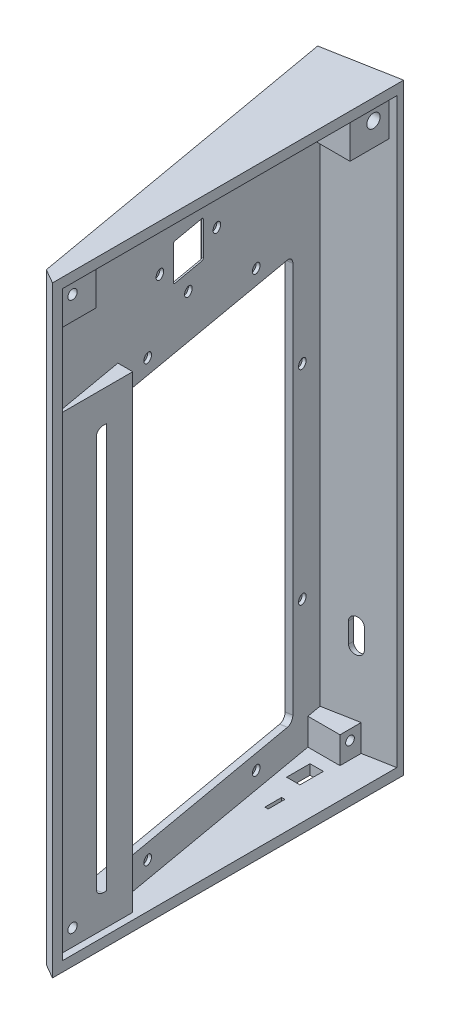
SolidWorks part; units mm, degrees
ref_plane "前视基准面" through (0, 0, 0) normal (0, 0, 1) x (1, 0, 0)
ref_plane "上视基准面" through (0, 0, 0) normal (0, 1, 0) x (1, 0, 0)
ref_plane "右视基准面" through (0, 0, 0) normal (1, 0, 0) x (0, 0, -1)
other "Configuration Table"
sketch "草图1" plane through (0, 0, 0) normal (0, 1, 0) x (1, 0, 0)
  line L0 (82.9035, -37.3993) -> (82.9035, -142.3993)
  line L1 (82.9035, -142.3993) -> (78.5734, -139.8993)
  line L2 (78.5734, -139.8993) -> (61.2086, -41.4185)
  line L3 (61.2086, -41.4185) -> (82.9035, -37.3993)
  dimension "D1" = 100
  dimension "D2" = 105
  dimension "D3" = 5
  dimension "D4" = 170
  dimension "D5" = 60
  dimension "D6" = 90.496
  dimension "D7" = 79.504
extrude "凸台-拉伸1" add sketch "草图1" along normal blind 180
sketch "草图5" plane through (52.2799, 0, -9.2184) normal (-0.9848, 0, 0.1736) x (0.1736, 0, 0.9848)
  line L0 (51.418, 180) -> (51.418, 0) construction
  line L1 (139.418, 12.5) -> (63.418, 12.5)
  line L2 (139.418, 12.5) -> (139.418, 133.5)
  line L3 (139.418, 133.5) -> (63.418, 133.5)
  line L4 (63.418, 12.5) -> (63.418, 133.5)
  line L5 (151.418, 180) -> (151.418, 0) construction
  line L6 (51.418, 0) -> (151.418, 0) construction
  dimension "D1" = 76
  dimension "D2" = 121
  dimension "D3" = 12
  dimension "D4" = 12
  dimension "D5" = 12.5
extrude "切除-拉伸2" cut sketch "草图5" against normal blind 2
sketch "草图7" plane through (82.9035, 0, 0) normal (1, 0, 0) x (0, 0, -1)
  line L8 (-139.3993, 3) -> (-40.3993, 3)
  line L9 (-40.3993, 3) -> (-40.3993, 177)
  line L10 (-40.3993, 177) -> (-139.3993, 177)
  line L11 (-139.3993, 177) -> (-139.3993, 3)
  line L12 (-139.3993, 3) -> (-40.3993, 3)
  line L13 (-40.3993, 3) -> (-40.3993, 177)
  line L14 (-40.3993, 177) -> (-139.3993, 177)
  line L15 (-139.3993, 177) -> (-139.3993, 3)
  dimension "D1" = 3
extrude "切除-拉伸3" cut sketch "草图7" against normal up to surface (19.8438 mm away) up to face at (71.8606, 73, 90.3116)
sketch "草图10" plane through (54.2496, 0, -9.5657) normal (0.9848, 0, -0.1736) x (-0.1736, 0, -0.9848)
  line L1 (-63.418, 12.5) -> (-59.918, 12.5) construction
  line L2 (-63.418, 12.5) -> (-63.418, 42.5) construction
  line L3 (-63.418, 42.5) -> (-59.918, 42.5) construction
  line L4 (-59.918, 12.5) -> (-59.918, 42.5) construction
  line L5 (-63.418, 133.5) -> (-59.918, 133.5) construction
  line L6 (-63.418, 133.5) -> (-63.418, 103.5) construction
  line L7 (-63.418, 103.5) -> (-59.918, 103.5) construction
  line L8 (-59.918, 133.5) -> (-59.918, 103.5) construction
  circle A0 centre (-59.918, 103.5) radius 1.4
  circle A1 centre (-59.918, 42.5) radius 1.4
  dimension "D1" = 30
  dimension "D2" = 30
  dimension "D3" = 3.5
  dimension "D4" = 3.5
extrude "切除-拉伸5" cut sketch "草图10" against normal blind 1
sketch "草图11" plane through (54.2496, 0, -9.5657) normal (0.9848, 0, -0.1736) x (-0.1736, 0, -0.9848)
  line L0 (-76.918, 8) -> (-116.918, 8) construction
  line L1 (-63.418, 133.5) -> (-76.918, 133.5) construction
  line L2 (-63.418, 133.5) -> (-63.418, 138) construction
  line L3 (-63.418, 138) -> (-76.918, 138) construction
  line L4 (-76.918, 133.5) -> (-76.918, 138) construction
  line L5 (-63.418, 12.5) -> (-76.918, 12.5) construction
  line L6 (-63.418, 12.5) -> (-63.418, 8) construction
  line L7 (-63.418, 8) -> (-76.918, 8) construction
  line L8 (-76.918, 12.5) -> (-76.918, 8) construction
  line L9 (-76.918, 138) -> (-116.918, 138) construction
  circle A0 centre (-116.918, 138) radius 1.4
  circle A1 centre (-76.918, 138) radius 1.4
  circle A2 centre (-116.918, 8) radius 1.4
  circle A3 centre (-76.918, 8) radius 1.4
  dimension "D1" = 13.5
  dimension "D2" = 4.5
  dimension "D3" = 13.5
  dimension "D4" = 4.5
  dimension "D5" = 40
  dimension "D6" = 40
extrude "切除-拉伸6" cut sketch "草图11" against normal blind 1
sketch "草图12" plane through (82.9035, 0, 0) normal (1, 0, 0) x (0, 0, -1)
  line L1 (-139.3993, 3) -> (-116.3993, 3)
  line L2 (-139.3993, 3) -> (-139.3993, 143)
  line L3 (-139.3993, 143) -> (-116.3993, 143)
  line L4 (-116.3993, 3) -> (-116.3993, 143)
  line L6 (-127.7343, 133.5) -> (-52.8889, 133.5) construction
  dimension "D1" = 9.5
  dimension "D2" = 23
extrude "凸台-拉伸3" add sketch "草图12" against normal up to surface (2.3874 mm away) up to face at (67.3631, 138, 64.8051)
sketch "草图13" plane through (54.2496, 0, -9.5657) normal (-0.9848, 0, 0.1736) x (0.1736, 0, 0.9848)
  line L4 (127.9081, 12.5) -> (139.418, 12.5)
  line L5 (139.418, 12.5) -> (139.418, 133.5)
  line L6 (139.418, 133.5) -> (127.9081, 133.5)
  line L7 (127.9081, 133.5) -> (127.9081, 12.5)
  line L8 (127.9081, 12.5) -> (139.418, 12.5)
  line L9 (139.418, 12.5) -> (139.418, 133.5)
  line L10 (139.418, 133.5) -> (127.9081, 133.5)
  line L11 (127.9081, 133.5) -> (127.9081, 12.5)
  dimension "D1" = 0
extrude "切除-拉伸7" cut sketch "草图13" against normal blind 2
sketch "草图14" plane through (52.2799, 0, -9.2184) normal (-0.9848, 0, 0.1736) x (0.1736, 0, 0.9848)
  line L0 (51.418, 180) -> (51.418, 0) construction
  line L1 (96.418, 151.5) -> (107.418, 151.5)
  line L2 (96.418, 151.5) -> (96.418, 162.5)
  line L3 (96.418, 162.5) -> (107.418, 162.5)
  line L4 (107.418, 151.5) -> (107.418, 162.5)
  line L5 (139.418, 133.5) -> (63.418, 133.5) construction
  line L6 (51.418, 180) -> (151.418, 180) construction
  dimension "D1" = 11
  dimension "D2" = 11
  dimension "D3" = 45
  dimension "D4" = 18
  dimension "D5" = 17.5
extrude "切除-拉伸8" cut sketch "草图14" against normal blind 2
sketch "草图17" plane through (9.4497, 0, 51.0074) normal (-0.1822, 0, -0.9833) x (-0.9833, 0, 0.1822)
  line L1 (-74.7037, 180) -> (-52.6396, 180)
  line L2 (-74.7037, 180) -> (-74.7037, 0)
  line L3 (-74.7037, 0) -> (-52.6396, 0)
  line L4 (-52.6396, 180) -> (-52.6396, 0)
extrude "凸台-拉伸9" add sketch "草图17" against normal blind 2
sketch "草图18" plane through (0, 0, 0) normal (0, -1, 0) x (1, 0, 0)
  line L0 (82.9035, 39.4333) -> (82.9035, 37.3993)
  line L1 (83.2679, 39.3658) -> (82.9035, 39.4333) construction
  line L2 (83.2679, 39.3658) -> (82.9035, 37.3993) construction
  line L3 (83.2679, 39.3658) -> (82.9035, 37.3993)
  line L4 (83.2679, 39.3658) -> (82.9035, 39.4333)
extrude "切除-拉伸9" cut sketch "草图18" against normal up to surface (180 mm away) up to face at (78.6267, 180, 73.3192)
sketch "草图19" plane through (0, 3, 0) normal (0, 1, 0) x (1, 0, 0)
  line L0 (82.9035, -40.3993) -> (82.9035, -36.7908) construction
  line L1 (77.596, -40.4166) -> (82.9035, -39.4333)
  line L2 (63.5225, -43.0238) -> (77.6894, -40.3993) construction
  line L3 (82.9035, -39.4333) -> (82.9035, -40.3993)
  line L4 (82.9035, -40.3993) -> (77.596, -40.4166)
extrude "切除-拉伸10" cut sketch "草图19" along normal up to surface (174 mm away) up to face at (77.507, 177, 80.5242)
sketch "草图20" plane through (82.9035, 0, 0) normal (1, 0, 0) x (0, 0, -1)
  line L1 (-139.3993, 143) -> (-116.3993, 143)
  line L2 (-139.3993, 143) -> (-139.3993, 3)
  line L3 (-139.3993, 3) -> (-116.3993, 3)
  line L4 (-116.3993, 143) -> (-116.3993, 3)
extrude "切除-拉伸11" cut sketch "草图20" against normal blind 2
sketch "草图21" plane through (54.2496, 0, -9.5657) normal (0.9848, 0, -0.1736) x (-0.1736, 0, -0.9848)
  line L0 (-107.418, 157) -> (-112.418, 157) construction
  line L1 (-107.418, 151.5) -> (-107.418, 162.5) construction
  line L2 (-101.918, 162.5) -> (-101.918, 167.5) construction
  line L3 (-107.418, 162.5) -> (-96.418, 162.5) construction
  line L4 (-96.418, 157) -> (-91.418, 157) construction
  line L5 (-96.418, 162.5) -> (-96.418, 151.5) construction
  line L6 (-101.918, 151.5) -> (-101.918, 146.5) construction
  line L7 (-96.418, 151.5) -> (-107.418, 151.5) construction
  circle A0 centre (-112.418, 157) radius 1.4
  circle A1 centre (-91.418, 157) radius 1.4
  circle A2 centre (-101.918, 146.5) radius 1.4
  circle A3 centre (-101.918, 167.5) radius 1.4
  dimension "D1" = 5
extrude "切除-拉伸12" cut sketch "草图21" against normal blind 1
sketch "草图23" plane through (80.9035, 0, 0) normal (1, 0, 0) x (0, 0, -1)
  line L0 (-51.4333, 8) -> (-51.4333, 26.4031) construction
  line L1 (-139.3993, 3) -> (-127.3993, 3)
  line L2 (-139.3993, 3) -> (-139.3993, 15)
  line L3 (-139.3993, 15) -> (-127.3993, 15)
  line L4 (-127.3993, 3) -> (-127.3993, 15)
  line L5 (-39.4333, 177) -> (-139.3993, 177) construction
  line L11 (-51.4333, 165) -> (-39.4333, 165)
  line L12 (-51.4333, 165) -> (-51.4333, 177)
  line L13 (-51.4333, 177) -> (-39.4333, 177)
  line L14 (-39.4333, 165) -> (-39.4333, 177)
  line L15 (-127.3993, 8) -> (-127.3993, 23.4787) construction
  line L17 (-127.3993, 165) -> (-139.3993, 165)
  line L18 (-127.3993, 165) -> (-127.3993, 177)
  line L19 (-127.3993, 177) -> (-139.3993, 177)
  line L20 (-139.3993, 165) -> (-139.3993, 177)
  dimension "D1" = 12
  dimension "D2" = 12
  dimension "D5" = 0
  dimension "D6" = 12
  dimension "D7" = 12
  dimension "D8" = 12
  dimension "D9" = 12
  dimension "D11" = 0
extrude "凸台-拉伸10" add sketch "草图23" against normal up to surface (0.3874 mm away) up to face at (73.5276, 157, 99.7657)
fillet "圆角4" radius 2 5 edges at (64.2772, 133.5, 53.0625) (78.4592, 133.5, 127.7343) (64.2772, 12.5, 53.0625) (77.4744, 12.5, 127.9079) (80.394, 12.5, 127.3931)
sketch "草图26" plane through (0, 177, 0) normal (0, 1, 0) x (1, 0, 0)
  line L3 (63.1752, -41.0542) -> (71.9242, -39.4333)
  line L4 (71.9242, -39.4333) -> (62.8894, -39.4333)
  line L5 (62.8894, -39.4333) -> (63.1752, -41.0542)
  line L6 (63.1752, -41.0542) -> (71.9242, -39.4333)
  line L7 (71.9242, -39.4333) -> (62.8894, -39.4333)
  line L8 (62.8894, -39.4333) -> (63.1752, -41.0542)
  dimension "D1" = 0
extrude "切除-拉伸15" cut sketch "草图26" against normal up to next
sketch "草图27" plane through (82.9035, 0, 0) normal (1, 0, 0) x (0, 0, -1)
  line L1 (-39.4333, 3) -> (-47.4333, 3)
  line L2 (-39.4333, 3) -> (-39.4333, 11)
  line L3 (-39.4333, 11) -> (-47.4333, 11)
  line L4 (-47.4333, 3) -> (-47.4333, 11)
  dimension "D1" = 8
  dimension "D2" = 8
extrude "凸台-拉伸11" add sketch "草图27" against normal up to surface (18.6035 mm away) up to face at (73.5276, 157, 99.7657)
sketch "草图28" plane through (82.9035, 0, 0) normal (1, 0, 0) x (0, 0, -1)
  line L1 (-47.4333, 3) -> (-39.4333, 3)
  line L2 (-47.4333, 3) -> (-47.4333, 11)
  line L3 (-47.4333, 11) -> (-39.4333, 11)
  line L4 (-39.4333, 3) -> (-39.4333, 11)
extrude "切除-拉伸16" cut sketch "草图28" against normal blind 9
sketch "草图29" plane through (0, 11, 0) normal (0, -1, 0) x (1, 0, 0)
  line L3 (73.9035, 41.1006) -> (73.9035, 39.4333)
  line L4 (73.9035, 39.4333) -> (82.9035, 39.4333)
  line L5 (82.9035, 39.4333) -> (73.9035, 41.1006)
  line L6 (73.9035, 41.1006) -> (73.9035, 39.4333)
  line L7 (73.9035, 39.4333) -> (82.9035, 39.4333)
  line L11 (82.9035, 39.4333) -> (73.9035, 41.1006)
  dimension "D1" = 0
extrude "凸台-拉伸12" add sketch "草图29" along normal up to surface (8 mm away) up to face at (77.0227, 3, 85.6663)
sketch "草图30" plane through (0, 3, 0) normal (0, -1, 0) x (1, 0, 0)
  line L3 (71.9242, 39.4333) -> (63.1752, 41.0542)
  line L4 (63.1752, 41.0542) -> (62.8894, 39.4333)
  line L5 (62.8894, 39.4333) -> (71.9242, 39.4333)
  line L6 (71.9242, 39.4333) -> (63.1752, 41.0542)
  line L7 (63.1752, 41.0542) -> (62.8894, 39.4333)
  line L8 (62.8894, 39.4333) -> (71.9242, 39.4333)
  dimension "D1" = 0
extrude "切除-拉伸17" cut sketch "草图30" against normal up to next
sketch "草图31" plane through (0, 0, 0) normal (0, -1, 0) x (1, 0, 0)
  line L1 (82.9035, 37.3993) -> (68.9035, 37.3993) construction
  line L2 (82.9035, 37.3993) -> (82.9035, 51.3993) construction
  line L3 (82.9035, 51.3993) -> (68.9035, 51.3993) construction
  line L4 (68.9035, 37.3993) -> (68.9035, 51.3993) construction
  line L5 (68.9035, 51.3993) -> (72.9035, 51.3993)
  line L6 (68.9035, 51.3993) -> (68.9035, 58.3993)
  line L7 (68.9035, 58.3993) -> (72.9035, 58.3993)
  line L8 (72.9035, 51.3993) -> (72.9035, 58.3993)
  dimension "D1" = 14
  dimension "D2" = 14
  dimension "D3" = 7
  dimension "D4" = 4
extrude "切除-拉伸18" cut sketch "草图31" against normal up to next
ref_plane "基准面1" through (0, 0, 37.3993) normal (0, 0, -1) x (-1, 0, 0)
ref_plane "基准面2" through (0, 0, 39.7193) normal (0, 0, -1) x (-1, 0, 0)
sketch "草图32" plane through (0, 0, 39.7193) normal (0, 0, -1) x (-1, 0, 0)
  line L0 (-72.7086, 36) -> (-72.7086, 30) construction
  line L1 (-70.7086, 36) -> (-70.7086, 30)
  line L2 (-74.7086, 36) -> (-74.7086, 30)
  line L3 (-82.9035, 180) -> (-61.2086, 180) construction
  line L4 (-61.2086, 180) -> (-61.2086, 0) construction
  arc A0 (-70.7086, 36) -> (-74.7086, 36) centre (-72.7086, 36) ccw
  arc A1 (-74.7086, 30) -> (-70.7086, 30) centre (-72.7086, 30) ccw
  point P2 (-72.7086, 33)
  point P9 (-72.7086, 28)
  point P10 (-72.7086, 38)
  dimension "D1" = 147
  dimension "D2" = 10
  dimension "D3" = 4
  dimension "D4" = 9.5
extrude "切除-拉伸23" cut sketch "草图32" against normal up to surface (1.9733 mm away) up to face at (75.3083, 89, 40.8404)
ref_plane "基准面4" through (0, 0, 40.2193) normal (0, 0, -1) x (-1, 0, 0)
sketch "草图35" plane through (0, 0, 40.2193) normal (0, 0, -1) x (-1, 0, 0)
  line L0 (-74.7086, 36) -> (-74.7086, 30) construction
  line L1 (-76.7086, 41) -> (-68.7086, 41)
  line L2 (-76.7086, 41) -> (-76.7086, 25)
  line L3 (-76.7086, 25) -> (-68.7086, 25)
  line L4 (-68.7086, 41) -> (-68.7086, 25)
  line L5 (-70.7086, 30) -> (-70.7086, 36) construction
  arc A0 (-70.7086, 36) -> (-74.7086, 36) centre (-72.7086, 36) ccw construction
  arc A1 (-74.7086, 30) -> (-70.7086, 30) centre (-72.7086, 30) ccw construction
  dimension "D1" = 5
  dimension "D2" = 5
  dimension "D3" = 2
  dimension "D4" = 2
extrude "切除-拉伸25" cut sketch "草图35" along normal up to surface (0.1902 mm away) up to face at (72.0561, 90, 39.4089)
fillet "圆角5" radius 0.5 4 edges at (76.7086, 25, 39.3831) (76.7086, 41, 39.3831) (68.7086, 25, 40.1241) (68.7086, 41, 40.1241)
sketch "草图36" plane through (0, 0, 0) normal (0, -1, 0) x (1, 0, 0)
  line L1 (82.9035, 37.3993) -> (74.4035, 37.3993) construction
  line L2 (82.9035, 37.3993) -> (82.9035, 64.3993) construction
  line L3 (82.9035, 64.3993) -> (74.4035, 64.3993) construction
  line L4 (74.4035, 37.3993) -> (74.4035, 64.3993) construction
  line L5 (74.4035, 64.3993) -> (73.4035, 64.3993)
  line L6 (74.4035, 64.3993) -> (74.4035, 69.3993)
  line L7 (74.4035, 69.3993) -> (73.4035, 69.3993)
  line L8 (73.4035, 64.3993) -> (73.4035, 69.3993)
  dimension "D1" = 8.5
  dimension "D2" = 27
  dimension "D3" = 1
  dimension "D4" = 5
extrude "切除-拉伸26" cut sketch "草图36" against normal up to next
sketch "草图37" plane through (0, 0, 0) normal (0, -1, 0) x (1, 0, 0)
  line L0 (73.4035, 66.8993) -> (74.4035, 66.8993) construction
  line L1 (73.4035, 69.3993) -> (73.4035, 64.3993) construction
  line L2 (74.4035, 64.3993) -> (74.4035, 69.3993) construction
  line L3 (73.9035, 64.3993) -> (73.9035, 69.3993) construction
  line L4 (73.4035, 64.3993) -> (74.4035, 64.3993) construction
  line L5 (74.4035, 69.3993) -> (73.4035, 69.3993) construction
  line L7 (74.9035, 69.8993) -> (72.9035, 69.8993)
  line L8 (74.9035, 69.8993) -> (74.9035, 63.8993)
  line L9 (74.9035, 63.8993) -> (72.9035, 63.8993)
  line L10 (72.9035, 69.8993) -> (72.9035, 63.8993)
  line L11 (74.9035, 69.8993) -> (72.9035, 63.8993) construction
  line L12 (74.9035, 63.8993) -> (72.9035, 69.8993) construction
  point P12 (73.9035, 66.8993)
  dimension "D1" = 6
  dimension "D2" = 2
extrude "切除-拉伸27" cut sketch "草图37" against normal blind 1
sketch "草图38" plane through (73.9035, 0, 0) normal (1, 0, 0) x (0, 0, -1)
  line L0 (-47.4333, 3) -> (-41.1006, 3) construction
  line L1 (-47.4333, 11) -> (-44.4333, 11) construction
  line L2 (-47.4333, 11) -> (-47.4333, 8) construction
  line L3 (-47.4333, 8) -> (-44.4333, 8) construction
  line L4 (-44.4333, 11) -> (-44.4333, 8) construction
  line L5 (-47.4333, 11) -> (-47.4333, 3) construction
  circle A0 centre (-44.4333, 8) radius 1.3
  dimension "D1" = 5
  dimension "D2" = 3
extrude "切除-拉伸28" cut sketch "草图38" against normal blind 3 contours A0
sketch "草图39" plane through (80.9035, 0, 0) normal (1, 0, 0) x (0, 0, -1)
  line L0 (-47.4333, 10.1358) -> (-47.4333, 2.8866) construction
  line L4 (-39.8038, 177) -> (-51.4333, 177) construction
  line L5 (-47.4333, 169) -> (-39.8038, 169) construction
  line L6 (-47.4333, 169) -> (-47.4333, 177) construction
  line L7 (-47.4333, 177) -> (-39.8038, 177) construction
  line L8 (-39.8038, 169) -> (-39.8038, 177) construction
  line L10 (-47.4333, 169) -> (-44.4333, 169) construction
  line L11 (-47.4333, 169) -> (-47.4333, 172) construction
  line L12 (-47.4333, 172) -> (-44.4333, 172) construction
  line L13 (-44.4333, 169) -> (-44.4333, 172) construction
  circle A0 centre (-44.4333, 172) radius 2
  dimension "D1" = 8
  dimension "D2" = 3
  dimension "D3" = 3
extrude "切除-拉伸30" cut sketch "草图39" against normal blind 3
sketch "草图40" plane through (80.9035, 0, 0) normal (1, 0, 0) x (0, 0, -1)
  line L1 (-127.3993, 177) -> (-131.3993, 177) construction
  line L2 (-127.3993, 177) -> (-127.3993, 171) construction
  line L3 (-127.3993, 171) -> (-131.3993, 171) construction
  line L4 (-131.3993, 177) -> (-131.3993, 171) construction
  line L5 (-131.3993, 171) -> (-134.3993, 171) construction
  line L6 (-131.3993, 171) -> (-131.3993, 172) construction
  line L7 (-131.3993, 172) -> (-134.3993, 172) construction
  line L8 (-134.3993, 171) -> (-134.3993, 172) construction
  line L9 (-139.3993, 3) -> (-134.3993, 3) construction
  line L10 (-139.3993, 3) -> (-139.3993, 8) construction
  line L11 (-139.3993, 8) -> (-134.3993, 8) construction
  line L12 (-134.3993, 3) -> (-134.3993, 8) construction
  circle A0 centre (-134.3993, 172) radius 1.4
  circle A1 centre (-134.3993, 8) radius 1.4
  dimension "D5" = 5
  dimension "D1" = 6
  dimension "D2" = 4
  dimension "D3" = 3
  dimension "D4" = 1
  dimension "D6" = 5
extrude "切除-拉伸31" cut sketch "草图40" against normal blind 2
sketch "草图42" plane through (54.2496, 0, -9.5657) normal (-0.9848, 0, 0.1736) x (0.1736, 0, 0.9848)
  line L3 (139.0778, 15) -> (139.0778, 13.3842)
  line L4 (139.418, 14.5) -> (139.418, 15)
  line L5 (139.418, 15) -> (139.0778, 15)
  line L6 (139.0778, 15) -> (139.0778, 13.3842)
  line L7 (139.418, 14.5) -> (139.418, 15)
  line L8 (139.418, 15) -> (139.0778, 15)
  arc A1 (139.0778, 13.3842) -> (139.418, 14.5) centre (137.418, 14.5) ccw
  arc A2 (139.0778, 13.3842) -> (139.418, 14.5) centre (137.418, 14.5) ccw
  dimension "D1" = 0
extrude "切除-拉伸34" cut sketch "草图42" against normal up to surface (2 mm away) up to face at (79.6913, 73, 123.2038)
chamfer "倒角1" distance 2 distance2 1.5 4 edges at (69.9778, 151.5, 91.1513) (69.0228, 157, 85.7348) (69.9778, 162.5, 91.1513) (70.9329, 157, 96.5677) first distance on face at (69.9778, 157, 91.1513)
fillet "圆角6" radius 0.5 4 edges at (72.6563, 151.5, 96.2638) (72.6563, 162.5, 96.2638) (70.7462, 162.5, 85.431) (70.7462, 151.5, 85.431)
sketch "草图43" plane through (56.2192, 0, -9.913) normal (-0.9848, 0, 0.1736) x (0.1736, 0, 0.9848)
  line L4 (139.418, 14.5) -> (139.418, 131.5)
  line L5 (137.418, 133.5) -> (128.2608, 133.5)
  line L6 (128.2608, 133.5) -> (128.2608, 12.5)
  line L7 (128.2608, 12.5) -> (137.418, 12.5)
  line L8 (139.418, 14.5) -> (139.418, 131.5)
  line L9 (137.418, 133.5) -> (128.2608, 133.5)
  line L10 (128.2608, 133.5) -> (128.2608, 12.5)
  line L11 (128.2608, 12.5) -> (137.418, 12.5)
  arc A2 (139.418, 131.5) -> (137.418, 133.5) centre (137.418, 131.5) ccw
  arc A3 (137.418, 12.5) -> (139.418, 14.5) centre (137.418, 14.5) ccw
  arc A4 (139.418, 131.5) -> (137.418, 133.5) centre (137.418, 131.5) ccw
  arc A5 (137.418, 12.5) -> (139.418, 14.5) centre (137.418, 14.5) ccw
  dimension "D1" = 0
extrude "切除-拉伸35" cut sketch "草图43" against normal blind 1
